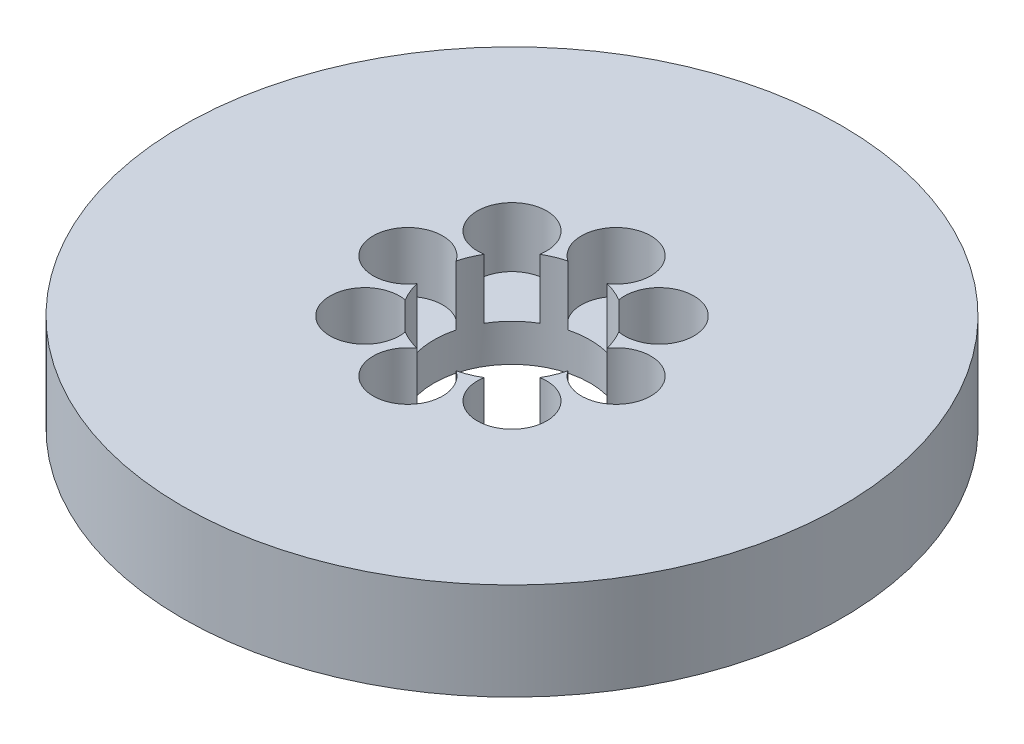
SolidWorks part; units mm, degrees
ref_plane "Front Plane" through (0, 0, 0) normal (0, 0, 1) x (1, 0, 0)
ref_plane "Top Plane" through (0, 0, 0) normal (0, 1, 0) x (1, 0, 0)
ref_plane "Right Plane" through (0, 0, 0) normal (1, 0, 0) x (0, 0, -1)
sketch "Sketch1" plane through (0, 0, 0) normal (0, 1, 0) x (1, 0, 0)
  circle A0 centre (0, 0) radius 95
  dimension "FLANGE_OD" = 190
extrude "Boss-Extrude1" add sketch "Sketch1" along normal blind 28
sketch "Sketch2" plane through (0, 0, 0) normal (0, 1, 0) x (1, 0, 0)
  circle A0 centre (0, 0) radius 22.5
  dimension "BORE_D" = 45
extrude "Cut-Extrude1" cut sketch "Sketch2" along normal through all
sketch "Sketch3" plane through (0, 28, 0) normal (0, 1, 0) x (1, 0, 0)
  circle A0 centre (0, 0) radius 30.0148 construction
  circle A1 centre (-30.0148, 0) radius 10
  dimension "BOLT_D" = 20
  dimension "BOLT_PCD" = 60.0296
extrude "Cut-Extrude2" cut sketch "Sketch3" against normal blind 17.231
pattern_circular "CirPattern1" count 8 over 360 about axis through (0, 0, 0) along (0, 1, 0) of "Cut-Extrude2"
